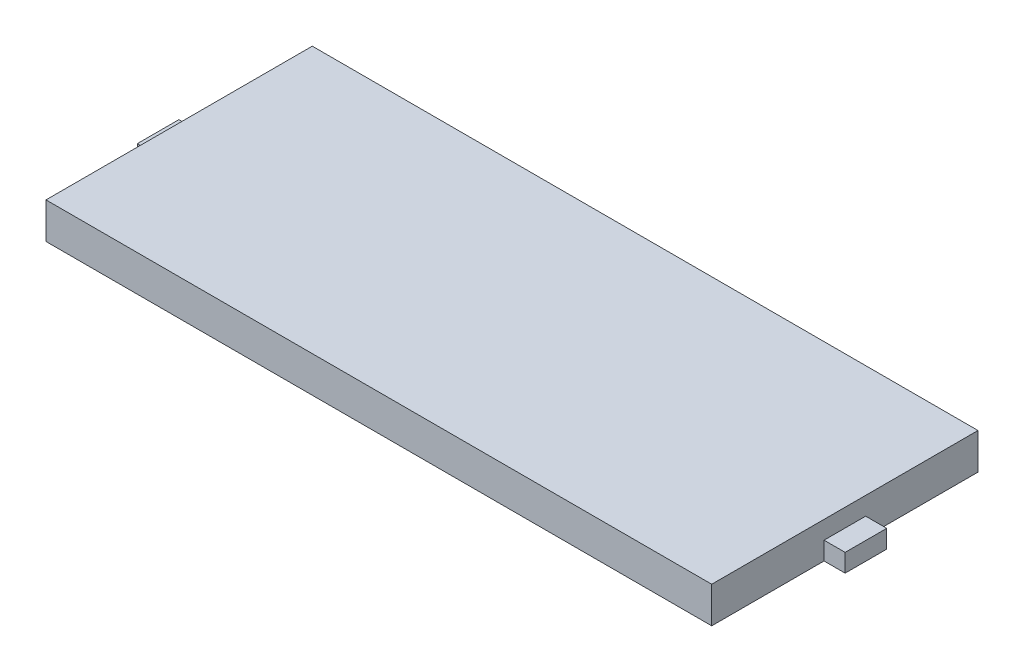
SolidWorks part; units mm, degrees
ref_plane "Front Plane" through (0, 0, 0) normal (0, 0, 1) x (1, 0, 0)
ref_plane "Top Plane" through (0, 0, 0) normal (0, 1, 0) x (1, 0, 0)
ref_plane "Right Plane" through (0, 0, 0) normal (1, 0, 0) x (0, 0, -1)
sketch "Sketch1" plane through (0, 0, 0) normal (0, 1, 0) x (1, 0, 0)
  line L1 (-6, -2.4) -> (6, -2.4)
  line L2 (-6, -2.4) -> (-6, 2.4)
  line L3 (-6, 2.4) -> (6, 2.4)
  line L4 (6, -2.4) -> (6, 2.4)
  line L5 (-6, -2.4) -> (6, 2.4) construction
  line L6 (-6, 2.4) -> (6, -2.4) construction
  point P0 (0, 0)
  dimension "D1" = 4.8
  dimension "D2" = 12
extrude "Boss-Extrude1" add sketch "Sketch1" along normal blind 0.65
sketch "Sketch2" plane through (0, 0, 0) normal (0, 1, 0) x (-1, 0, 0)
  line L0 (6, -2.4) -> (6, 2.4) construction
  line L1 (0.62, -0.375) -> (6.38, -0.375)
  line L2 (0.62, -0.375) -> (0.62, 0.375)
  line L3 (0.62, 0.375) -> (6.38, 0.375)
  line L4 (6.38, -0.375) -> (6.38, 0.375)
  line L5 (0.62, -0.375) -> (6.38, 0.375) construction
  line L6 (0.62, 0.375) -> (6.38, -0.375) construction
  point P0 (3.5, 0)
  point P5 (0, 0)
  dimension "D1" = 0.75
  dimension "D2" = 0.38
  dimension "D3" = 3.5
extrude "Boss-Extrude2" add sketch "Sketch2" along normal blind 0.325 separate body
extrude "Cut-Extrude1" cut sketch "Sketch2<2>" along normal blind 0.325
sketch "Sketch2<2>" plane through (0, 0, 0) normal (0, 1, 0) x (-1, 0, 0) same geometry as "Sketch2"
mirror "Mirror1" about plane through (0, 0, 0) normal (1, 0, 0) of bodies 102
mirror "Mirror2" about plane through (0, 0, 0) normal (1, 0, 0) of "Cut-Extrude1"
